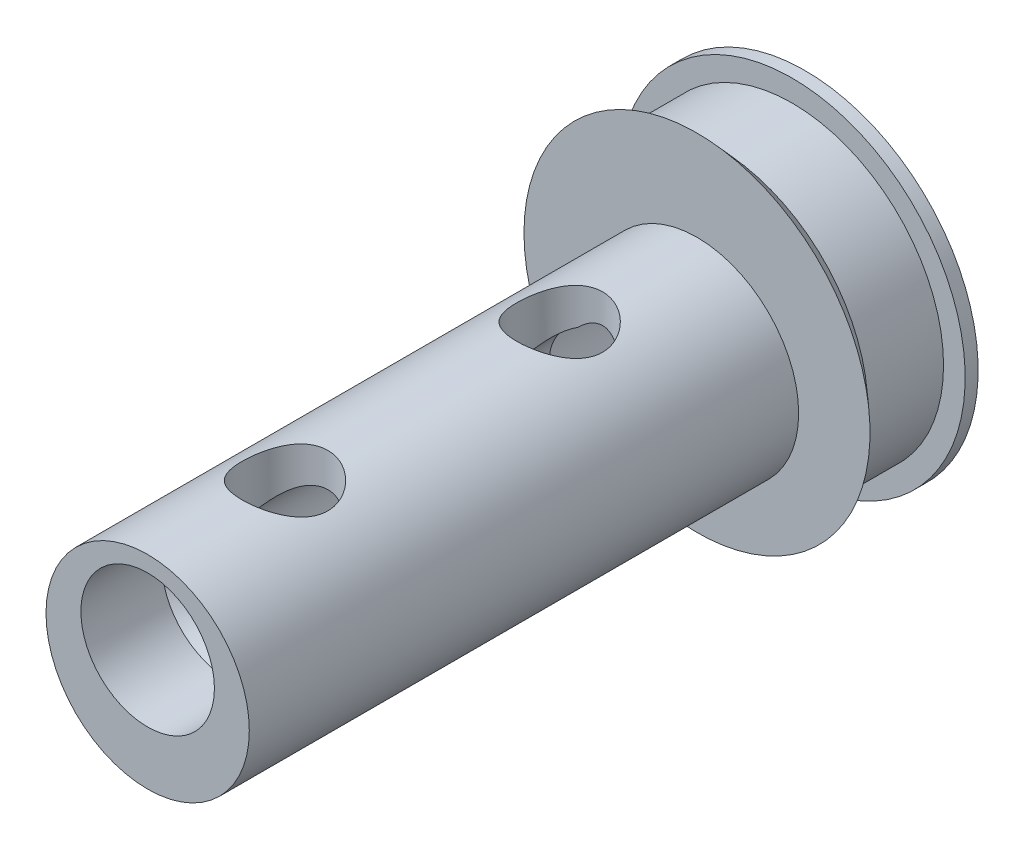
SolidWorks part; units mm, degrees
material "ABS"
ref_plane "Front Plane" through (0, 0, 0) normal (0, 0, 1) x (1, 0, 0)
ref_plane "Top Plane" through (0, 0, 0) normal (0, 1, 0) x (1, 0, 0)
ref_plane "Right Plane" through (0, 0, 0) normal (1, 0, 0) x (0, 0, -1)
sketch "Sketch1" plane through (0, 0, 0) normal (0, 0, 1) x (1, 0, 0)
  circle A0 centre (0, 1.75) radius 6.175
  circle A1 centre (0, 0) radius 9.525 construction
  circle A2 centre (0, 0) radius 9.525 construction
  circle A3 centre (0, 0) radius 9.4
  dimension "D1" = 12.35
  dimension "D3" = 0.125
  dimension "D2" = 1.75
extrude "Boss-Extrude1" add sketch "Sketch1" against normal up to surface (50.8 mm away)
ref_axis "Axis1" through (0, 1.75, -50.8) along (0, 0, 1)
sketch "Sketch3" plane through (0, 0, 0) normal (1, 0, 0) x (0, 0, -1)
  line L0 (60.8, 11.45) -> (54.8, 11.45)
  line L2 (50.8, 7.925) -> (54.8, 11.45)
  line L4 (60.8, 11.45) -> (60.8, 17.75)
  line L5 (60.8, 17.75) -> (59.6, 17.75)
  line L7 (59.6, 17.75) -> (59.6, 15.75)
  line L8 (59.6, 15.75) -> (52.6, 15.75)
  line L9 (50.8, 9.4) -> (0, 9.4) construction
  line L10 (52.6, 15.75) -> (50.8, 17.75)
  line L12 (50.8, 17.75) -> (50.8, 7.925)
  line L15 (50.8, 1.75) -> (0, 1.75) construction
  point P2 (0, 0)
  point P12 (50.8, 15.6572)
  point P16 (25.4, 9.4)
  dimension "D1" = 9.7
  dimension "D3" = 10
  dimension "D2" = 6
  dimension "D4" = 1.2
  dimension "D5" = 2
  dimension "D6" = 7
  dimension "D7" = 14
  dimension "D8" = 8.35
revolve "Revolve1" add sketch "Sketch3" angle 360 about axis through (0, 1.75, -50.8) along (0, 0, 1)
ref_plane "Plane1" through (0, 0, -30.4) normal (0, 0, 1) x (1, 0, 0)
sketch "Sketch9" plane through (0, 0, 0) normal (1, 0, 0) x (0, 0, -1)
  line L0 (43.3, 7.925) -> (7.5, 7.925)
  line L2 (43.3, 7.925) -> (41.625, 6.25)
  line L3 (41.625, 6.25) -> (9.175, 6.25)
  line L4 (9.175, 6.25) -> (7.5, 7.925)
  line L5 (50.8, 1.75) -> (0, 1.75) construction
  line L6 (0, 9.4) -> (0, -9.4) construction
  line L7 (50.8, 17.75) -> (50.8, -14.25) construction
  dimension "D1" = 45
  dimension "D2" = 45
  dimension "D3" = 4.5
  dimension "D4" = 7.5
  dimension "D5" = 7.5
revolve "Revolve2" add sketch "Sketch9" angle 360 about axis through (0, 1.75, -50.8) along (0, 0, 1)
sketch "Sketch8" plane through (0, 0, 0) normal (0, 1, 0) x (1, 0, 0)
  circle A0 centre (0, 38.1) radius 3.9688
  circle A1 centre (0, 12.7) radius 3.9688
  dimension "D1" = 7.9375
extrude "Cut-Extrude3" cut sketch "Sketch8" along normal blind 26
